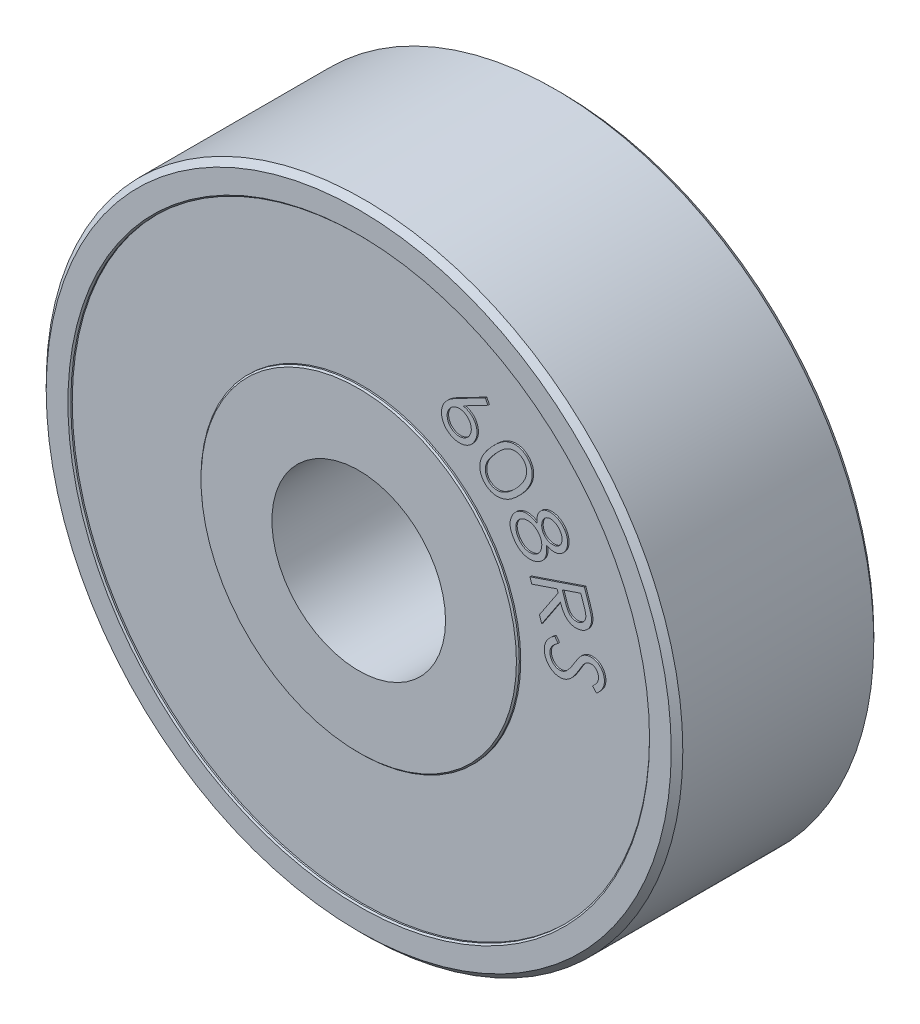
SolidWorks part; units mm, degrees
ref_plane "Front Plane" through (0, 0, 0) normal (0, 0, 1) x (1, 0, 0)
ref_plane "Top Plane" through (0, 0, 0) normal (0, 1, 0) x (1, 0, 0)
ref_plane "Right Plane" through (0, 0, 0) normal (1, 0, 0) x (0, 0, -1)
sketch "Sketch1" plane through (0, 0, 0) normal (0, 0, 1) x (1, 0, 0)
  circle A0 centre (0, 0) radius 11
  circle A1 centre (0, 0) radius 4
extrude "Boss-Extrude1" add sketch "Sketch1" along normal blind 7
sketch "Sketch2" plane through (0, 0, 7) normal (0, 0, 1) x (1, 0, 0)
  circle A0 centre (0, 0) radius 5.5
  circle A1 centre (0, 0) radius 10
extrude "Cut-Extrude1" cut sketch "Sketch2" against normal blind 0.1
extrude "Cut-Extrude2" cut sketch "Sketch2<2>" against normal blind 0.1 from offset 6.9 offset against normal yes
sketch "Sketch2<2>" plane through (0, 0, 7) normal (0, 0, 1) x (1, 0, 0) same geometry as "Sketch2"
chamfer "Chamfer1" distance 0.2 angle 45 4 edges at (4, 0, 0) (4, 0, 7) (11, 0, 7) (11, 0, 0)
chamfer "Chamfer2" distance 0.05 angle 45 4 edges at (5.5, 0, 7) (10, 0, 7) (10, 0, 0) (5.5, 0, 0)
sketch "Sketch3" plane through (0, 0, 0.1) normal (0, 0, -1) x (-1, 0, 0)
  circle A0 centre (0, 0) radius 6.5 construction
  text T0 "608RS" font "Century Gothic" height 2
extrude "Boss-Extrude2" add sketch "Sketch3" along normal blind 0.05
sketch "Sketch4" plane through (0, 0, 6.9) normal (0, 0, 1) x (1, 0, 0)
  circle A0 centre (0, 0) radius 6.5 construction
  text T0 "608RS" font "Century Gothic" height 2
extrude "Boss-Extrude3" add sketch "Sketch4" along normal blind 0.05
sketch "Sketch5" plane through (0, 0, 7) normal (0, 0, 1) x (1, 0, 0)
  circle A0 centre (0, 0) radius 4.2
  circle A1 centre (0, 0) radius 3
extrude "Boss-Extrude4" add sketch "Sketch5" against normal blind 7
